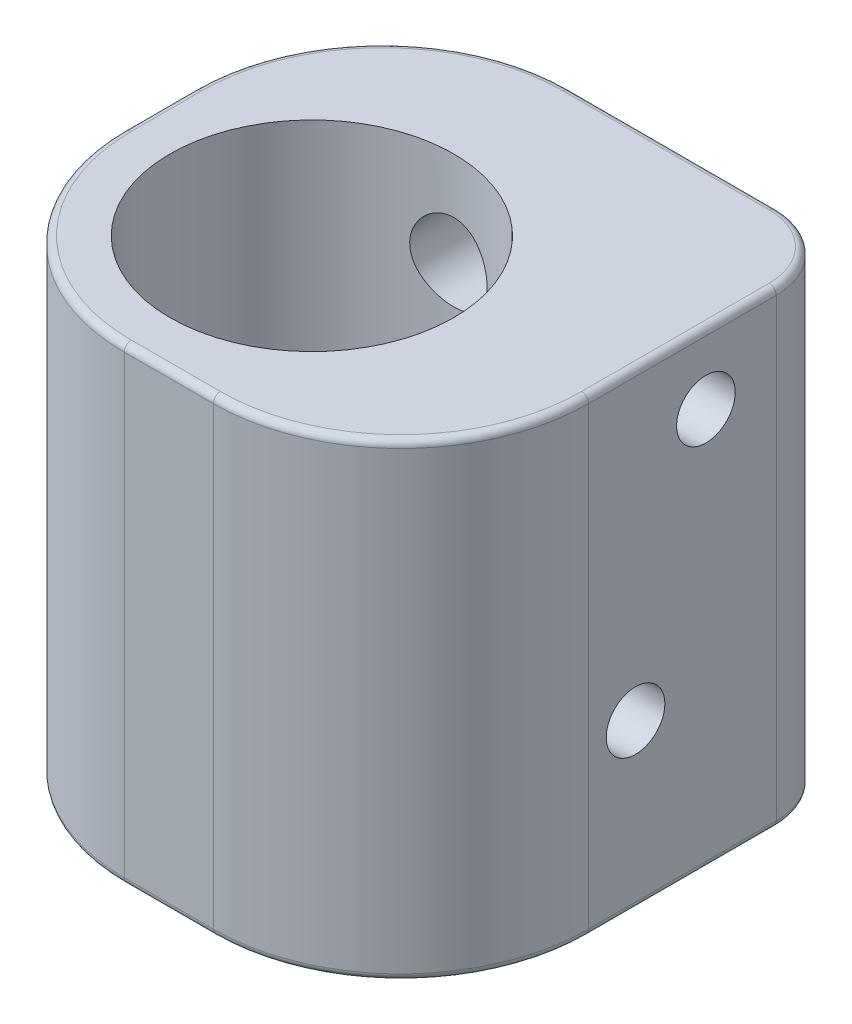
SolidWorks part; units mm, degrees
ref_plane "前视基准面" through (0, 0, 0) normal (0, 0, 1) x (1, 0, 0)
ref_plane "上视基准面" through (0, 0, 0) normal (0, 1, 0) x (1, 0, 0)
ref_plane "右视基准面" through (0, 0, 0) normal (1, 0, 0) x (0, 0, -1)
sketch "草图1" plane through (0, 0, 0) normal (0, 1, 0) x (1, 0, 0)
  line L0 (0, 0) -> (29713.2204, 0) construction
  line L1 (0, 0) -> (0, 29713.2204) construction
  line L3 (0, 11) -> (8.8, 11)
  line L4 (-8, 3) -> (-8, 0)
  line L5 (0, -8) -> (3.8, -8)
  line L6 (11.8, 8) -> (11.8, 0)
  circle A0 centre (0, 0) radius 6.05
  arc A1 (3.8, -8) -> (11.8, 0) centre (3.8, 0) ccw
  arc A2 (-8, 0) -> (0, -8) centre (0, 0) ccw
  arc A3 (0, 11) -> (-8, 3) centre (0, 3) ccw
  arc A4 (8.8, 11) -> (11.8, 8) centre (8.8, 8) cw
  dimension "D1" = 12.1
  dimension "D6" = 8
  dimension "D7" = 3
  dimension "D8" = 8
  dimension "D9" = 8
  dimension "D2" = 8
  dimension "D3" = 11.8
  dimension "D4" = 11
  dimension "D5" = 8
extrude "凸台-拉伸1" add sketch "草图1" along normal blind 20
sketch "草图2" plane through (11.8, 0, 0) normal (1, 0, 0) x (0, 0, -1)
  line L0 (11, 20) -> (11, 0) construction
  line L1 (0, 20) -> (8, 20) construction
  circle A0 centre (5, 17) radius 1
  circle A1 centre (2, 7) radius 1
  dimension "D1" = 3
  dimension "D2" = 10
  dimension "D3" = 2
  dimension "D5" = 6
  dimension "D6" = 3
extrude "切除-拉伸1" cut sketch "草图2" against normal blind 2
hole_wizard "M3 螺纹孔1" positions "草图3" profile "草图4" tap size "M3" standard "GB"
sketch "草图3" plane through (11.8, 0, 0) normal (1, 0, 0) x (0, 0, -1)
  point P0 (5, 17)
  point P3 (2, 7)
sketch "草图4" plane through (11.8, 17, -5) normal (0, 1, 0) x (0, 0, -1)
  line L0 (0, 0) -> (0, 7.7511)
  line L1 (0, 7.7511) -> (1.25, 7)
  line L2 (1.25, 7) -> (1.25, 0)
  line L5 (1.25, 0) -> (0, 0)
  line L10 (0, 7.7511) -> (-1.25, 7) construction
  line L11 (0, -6.35) -> (0, 107.95) construction
  dimension "螺纹孔钻头直径" = 2.5
  dimension "螺纹孔钻头深度" = 7
  dimension "导头角度" = 118
cosmetic thread "孔螺蚊线1" parameters "D1"=5, "D2"=3
cosmetic thread "孔螺蚊线2" parameters "D1"=5, "D2"=3
ref_axis "基准轴1" through (0, 20, 0) along (0, -1, 0)
hole_wizard "M4 螺纹孔1" positions "草图5" profile "草图6" tap size "M4" standard "GB"
sketch "草图5" plane through (3, 0, -11) normal (0, 0, 1) x (1, 0, 0)
  line L0 (-3, 20) -> (-3, 0) construction
  line L1 (-3, 20) -> (-11, 20) construction
  line L3 (5.8, 0) -> (-3, 0) construction
  point P0 (-3, 16)
  point P2 (-3, 4)
  dimension "D1" = 4
  dimension "D2" = 4
sketch "草图6" plane through (0, 16, -11) normal (1, 0, 0) x (0, 1, 0)
  line L0 (0, 0) -> (0, 12.4914)
  line L1 (0, 12.4914) -> (1.65, 11.5)
  line L2 (1.65, 11.5) -> (1.65, 0)
  line L5 (1.65, 0) -> (0, 0)
  line L10 (0, 12.4914) -> (-1.65, 11.5) construction
  line L11 (0, -6.35) -> (0, 107.95) construction
  dimension "螺纹孔钻头直径" = 3.3
  dimension "螺纹孔钻头深度" = 11.5
  dimension "导头角度" = 118
cosmetic thread "孔螺蚊线3" parameters "D1"=5.2493, "D2"=4
cosmetic thread "孔螺蚊线4" parameters "D1"=5.2493, "D2"=4
fillet "圆角1" radius 0.3 16 edges at (9.4569, 0, 5.6569) (1.9, 0, 8) (-5.6569, 0, 5.6569) (-8, 0, -1.5) (-5.6569, 0, -8.6569) (4.4, 0, -11) (10.9213, 0, -10.1213) (9.4569, 20, 5.6569) (1.9, 20, 8) (-5.6569, 20, 5.6569) (-8, 20, -1.5) (-5.6569, 20, -8.6569) (4.4, 20, -11) (10.9213, 20, -10.1213) (11.8, 0, -4) (11.8, 20, -4)
